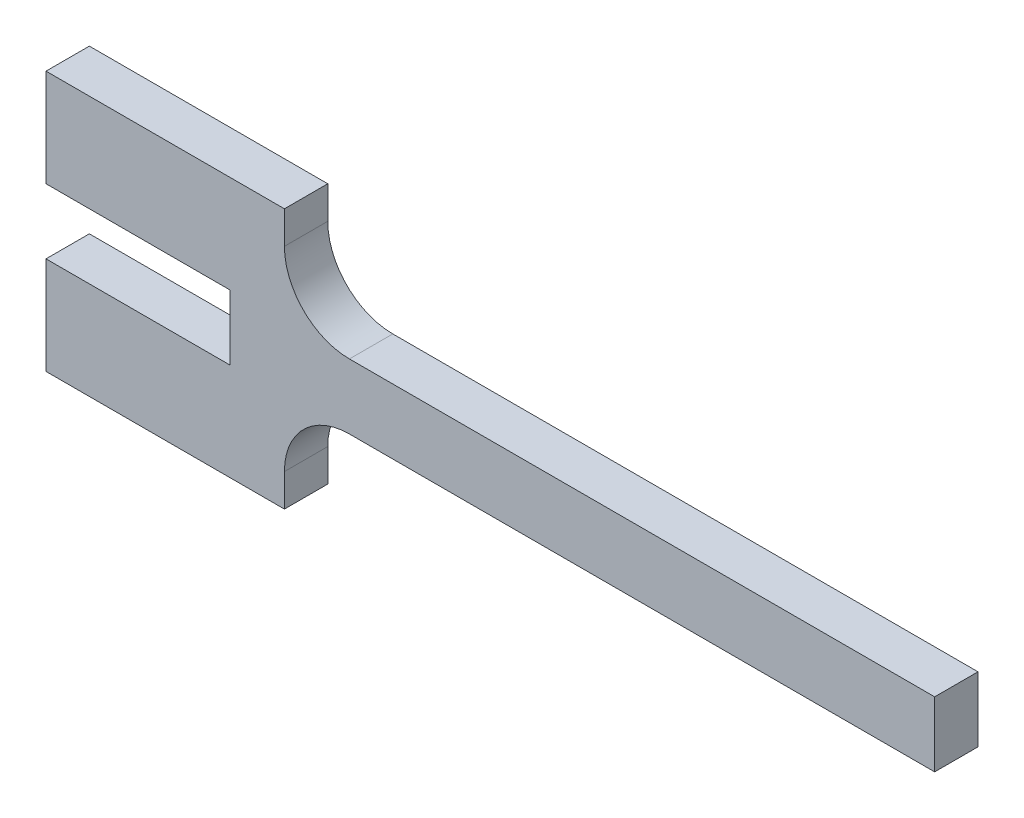
SolidWorks part; units mm, degrees
ref_plane "Front Plane" through (0, 0, 0) normal (0, 0, 1) x (1, 0, 0)
ref_plane "Top Plane" through (0, 0, 0) normal (0, 1, 0) x (1, 0, 0)
ref_plane "Right Plane" through (0, 0, 0) normal (1, 0, 0) x (0, 0, -1)
sketch "Sketch1" plane through (0, 0, 0) normal (0, 0, 1) x (1, 0, 0)
  line L0 (0, 0) -> (0, 4.5)
  line L1 (0, 4.5) -> (8.5, 4.5)
  line L2 (8.5, 4.5) -> (8.5, 7.5)
  line L3 (8.5, 7.5) -> (0, 7.5)
  line L4 (0, 7.5) -> (0, 12)
  line L5 (0, 12) -> (11, 12)
  line L6 (11, 12) -> (11, 10.5)
  line L7 (14, 7.5) -> (41, 7.5)
  line L8 (41, 7.5) -> (41, 4.5)
  line L9 (41, 4.5) -> (14, 4.5)
  line L10 (11, 1.5) -> (11, 0)
  line L11 (11, 0) -> (0, 0)
  arc A0 (14, 4.5) -> (11, 1.5) centre (14, 1.5) ccw
  arc A1 (11, 10.5) -> (14, 7.5) centre (14, 10.5) ccw
  point P17 (11, 7.5)
  dimension "D6" = 3
  dimension "D1" = 11
  dimension "D2" = 8.5
  dimension "D3" = 3
  dimension "D4" = 12
  dimension "D5" = 30
extrude "Boss-Extrude1" add sketch "Sketch1" along normal blind 2
